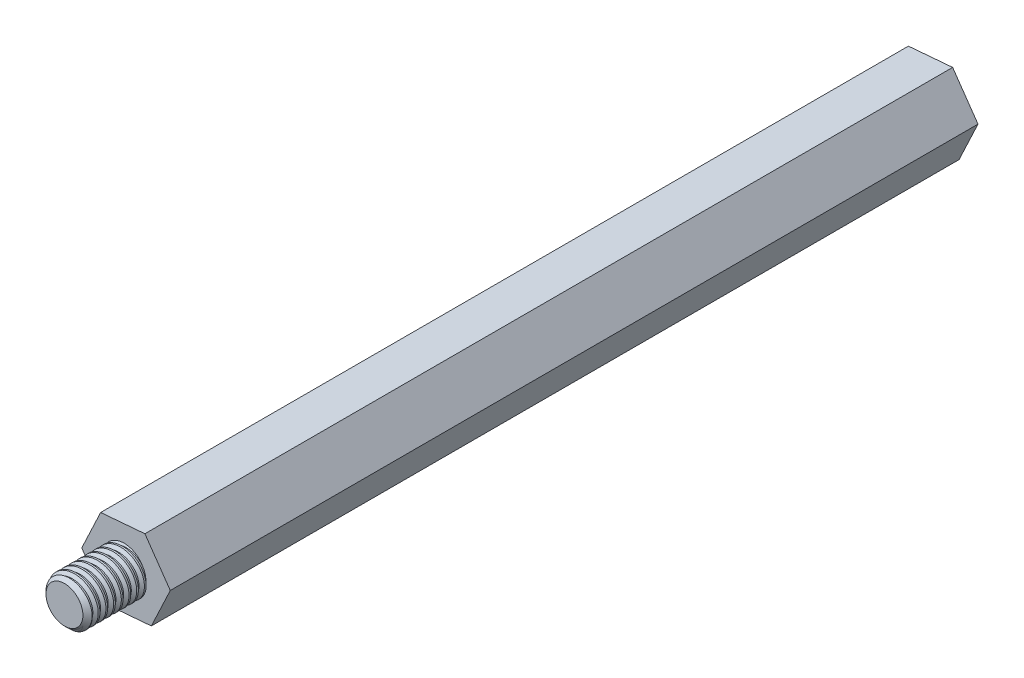
SolidWorks part; units mm, degrees
ref_plane "前视基准面" through (0, 0, 0) normal (0, 0, 1) x (1, 0, 0)
ref_plane "上视基准面" through (0, 0, 0) normal (0, 1, 0) x (1, 0, 0)
ref_plane "右视基准面" through (0, 0, 0) normal (1, 0, 0) x (0, 0, -1)
sketch "草图1" plane through (0, 0, 0) normal (0, 0, 1) x (1, 0, 0)
  line L1 (1.6473, -2.3706) -> (2.8766, 0.2414)
  line L2 (2.8766, 0.2414) -> (1.2293, 2.6119)
  line L3 (1.2293, 2.6119) -> (-1.6473, 2.3706)
  line L4 (-1.6473, 2.3706) -> (-2.8766, -0.2414)
  line L5 (-2.8766, -0.2414) -> (-1.2293, -2.6119)
  line L6 (-1.2293, -2.6119) -> (1.6473, -2.3706)
  circle A0 centre (0, 0) radius 1.5
  circle A1 centre (0, 0) radius 2.5 construction
  dimension "D1" = 3
  dimension "D2" = 5
extrude "凸台-拉伸1" add sketch "草图1" along normal blind 52.5 contours L5 L6 L1 L2 L3 L4 A0
hole_wizard "M3 螺纹孔1" positions "3D草图1" profile "草图2" tap size "M3" standard "GB"
sketch3d "3D草图1"
  point P0 (0, 0, 0)
  point P3 (0, 0, 0)
  point P5 (0, 0, 0)
  point P7 (0, 0, 0)
  point P9 (0, 0, 0)
sketch "草图2" plane through (0, 0, 0) normal (1, 0, 0) x (0, 1, 0)
  line L0 (0, 0) -> (0, 15.7511)
  line L1 (0, 15.7511) -> (1.25, 15)
  line L2 (1.25, 15) -> (1.25, 0)
  line L5 (1.25, 0) -> (0, 0)
  line L10 (0, 15.7511) -> (-1.25, 15) construction
  line L11 (0, -6.35) -> (0, 107.95) construction
  dimension "螺纹孔钻头直径" = 2.5
  dimension "螺纹孔钻头深度" = 15
  dimension "导头角度" = 118
cosmetic thread "孔螺蚊线1" parameters "D1"=10, "D2"=3
cosmetic thread "孔螺蚊线2" parameters "D1"=10, "D2"=3
cosmetic thread "孔螺蚊线3" parameters "D1"=10, "D2"=3
cosmetic thread "孔螺蚊线4" parameters "D1"=10, "D2"=3
cosmetic thread "孔螺蚊线5" parameters "D1"=10, "D2"=3
sketch "草图3" plane through (0, 0, 52.5) normal (0, 0, 1) x (1, 0, 0)
  circle A0 centre (0, 0) radius 1.5
  dimension "D1" = 3
extrude "凸台-拉伸2" add sketch "草图3" along normal blind 4
chamfer "倒角1" distance 0.3 angle 45 1 edges at (1.5, 0, 56.5)
sketch "草图4" plane through (0, 0, 56.5) normal (0, 0, 1) x (1, 0, 0)
  circle A0 centre (0, 0) radius 1.5 construction
  circle A1 centre (0, 0) radius 1.5
curve "螺旋线/涡状线1" pitch 0.5 height 4 turns 8
sketch "草图5" plane through (0, 0, 0) normal (0, 1, 0) x (1, 0, 0)
  line L0 (1.5432, -56.725) -> (1.5432, -56.275)
  line L1 (1.5432, -56.275) -> (1.2932, -56.45)
  line L2 (1.2932, -56.45) -> (1.2932, -56.55)
  line L3 (1.2932, -56.55) -> (1.5432, -56.725)
  line L4 (1.2932, -56.5) -> (1.5984, -56.5) construction
  line L7 (-1.2, -56.5) -> (1.2, -56.5) construction
  line L8 (-1.2, -56.5) -> (1.2, -56.5) construction
  dimension "D1" = 0.45
  dimension "D2" = 0.1
  dimension "D3" = 0.25
sweep "切除-扫描2" cut profiles "草图5" path "螺旋线/涡状线1"
